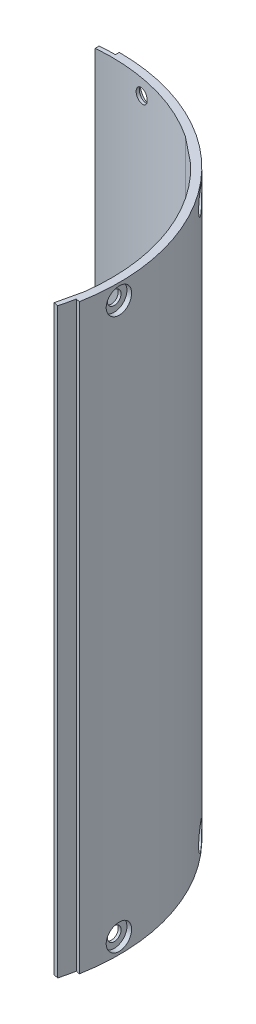
SolidWorks part; units mm, degrees
ref_plane "Спереди" through (0, 0, 0) normal (0, 0, 1) x (1, 0, 0)
ref_plane "Сверху" through (0, 0, 0) normal (0, 1, 0) x (1, 0, 0)
ref_plane "Справа" through (0, 0, 0) normal (1, 0, 0) x (0, 0, -1)
sketch "Эскиз2" plane through (0, 0, 0) normal (0, 1, 0) x (1, 0, 0)
  line L0 (0, -1000) -> (0, 49000) construction
  line L1 (47.1356, -12.7936) -> (48.2666, -13.0514)
  line L2 (33.9524, 35.3303) -> (27.0476, 40.8587) construction
  line L3 (48.5627, -6.5315) -> (46.5973, -15.1557) construction
  line L5 (33.9524, 35.3303) -> (27.0476, 40.8587)
  line L6 (48.5627, -6.5315) -> (46.5973, -15.1557) construction
  line L7 (-3.9968, 48.8367) -> (-3.9968, 49.84)
  line L10 (0, 50) -> (0, 49) construction
  line L12 (0, 0) -> (47.58, -10.8436) construction
  line L16 (47.58, -10.8436) -> (49.725, -11.3324) construction
  line L17 (47.1356, -12.7936) -> (48.5627, -6.5315)
  line L18 (49.1554, -9.1514) -> (50.1312, -9.3737)
  line L19 (0, 50) -> (0, 51)
  circle A0 centre (0, 0) radius 51 construction
  arc A1 (50.1312, -9.3737) -> (0, 51) centre (0, 0) ccw
  circle A2 centre (0, 0) radius 51 construction
  arc A3 (48.5627, -6.5315) -> (33.9524, 35.3303) centre (0, 0) ccw construction
  arc A4 (0, 51) -> (0, -51) centre (0, 0) ccw construction
  arc A5 (48.5627, -6.5315) -> (33.9524, 35.3303) centre (0, 0) ccw
  arc A6 (-3.9968, 48.8367) -> (27.0476, 40.8587) centre (0, 0) cw
  arc A7 (0, -51) -> (49.725, -11.3324) centre (0, 0) ccw construction
  arc A8 (49.725, -11.3324) -> (50.1312, -9.3737) centre (0, 0) ccw construction
  arc A9 (27.0476, 40.8587) -> (-27.0476, 40.8587) centre (0, 0) ccw construction
  arc A10 (0, 50) -> (-3.9968, 49.84) centre (0, 0) ccw
  arc A11 (49.1554, -9.1514) -> (48.2666, -13.0514) centre (0, 0) cw
  point P25 (48.6525, -11.088)
  dimension "D1" = 3.9968
  dimension "D2" = 4
extrude "Бобышка-Вытянуть2" add sketch "Эскиз2" along normal up to surface (149 mm away)
ref_plane "Плоскость5" through (51, 0, 0) normal (1, 0, 0) x (0, 0, -1)
sketch "Эскиз15" plane through (51, 0, 0) normal (1, 0, 0) x (0, 0, -1)
  line L0 (0, -1000) -> (0, 49000) construction
  circle A0 centre (0, 4) radius 3.25
  dimension "D1" = 6.5
  dimension "D2" = 4
extrude "Вырез-Вытянуть5" cut sketch "Эскиз15" against normal blind 1.3
sketch "Эскиз16" plane through (49.7, 0, 0) normal (1, 0, 0) x (0, 0, -1)
  circle A0 centre (0, 4) radius 3.25 construction
  circle A1 centre (0, 4) radius 3.25 construction
  circle A2 centre (0, 4) radius 1.75
  dimension "D1" = 3.5
extrude "Вырез-Вытянуть6" cut sketch "Эскиз16" against normal through all
pattern_circular "Круговой массив3" count 5 every 20 about axis through (0, 0, 0) along (0, 1, 0) skipping 1, 3 of "Вырез-Вытянуть5", "Вырез-Вытянуть6"
sketch "Эскиз17" plane through (51, 0, 0) normal (1, 0, 0) x (0, 0, -1)
  line L0 (0, -1000) -> (0, 49000) construction
  line L1 (51, 149) -> (-9.3737, 149) construction
  circle A0 centre (0, 145) radius 3.25
  circle A1 centre (0, 4) radius 3.25 construction
  dimension "D1" = 4
extrude "Вырез-Вытянуть7" cut sketch "Эскиз17" against normal blind 1.3
sketch "Эскиз18" plane through (49.7, 0, 0) normal (1, 0, 0) x (0, 0, -1)
  circle A0 centre (0, 145) radius 3.25 construction
  circle A1 centre (0, 145) radius 3.25 construction
  circle A2 centre (0, 145) radius 1.75
  circle A3 centre (0, 4) radius 1.75 construction
extrude "Вырез-Вытянуть8" cut sketch "Эскиз18" against normal through all
pattern_circular "Круговой массив5" count 5 every 20 about axis through (0, 149, 0) along (0, 1, 0) skipping 1, 3 of "Вырез-Вытянуть8", "Вырез-Вытянуть7"
